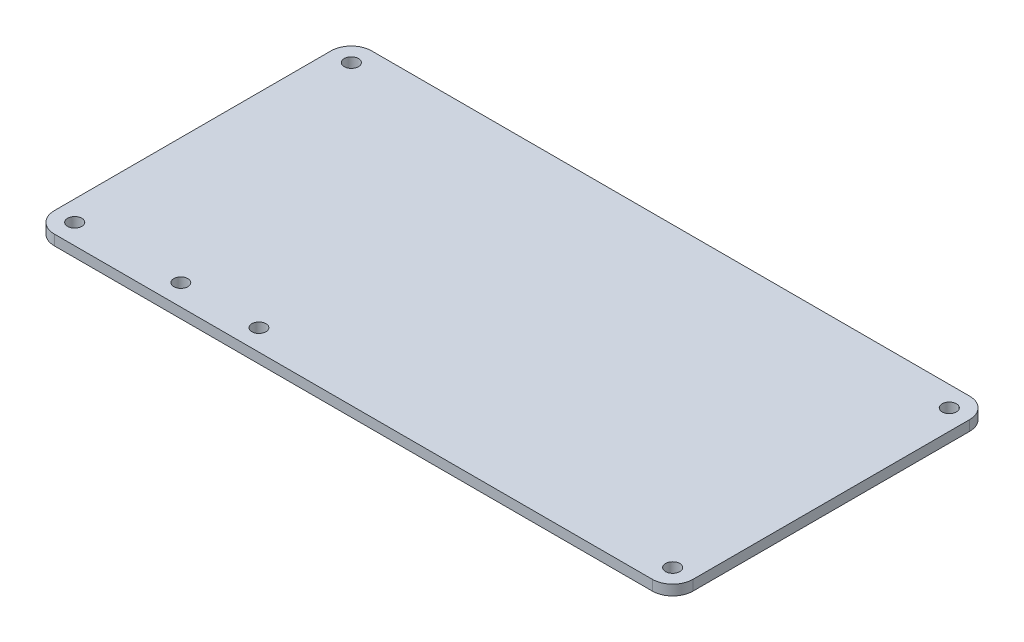
SolidWorks part; units mm, degrees
ref_plane "Front Plane" through (0, 0, 0) normal (0, 0, 1) x (1, 0, 0)
ref_plane "Top Plane" through (0, 0, 0) normal (0, 1, 0) x (1, 0, 0)
ref_plane "Right Plane" through (0, 0, 0) normal (1, 0, 0) x (0, 0, -1)
sketch "Sketch1" plane through (0, 0, 0) normal (0, 1, 0) x (1, 0, 0)
  line L0 (49.8475, 0) -> (49.8475, 49.53) construction
  line L1 (3.175, 0) -> (96.52, 0)
  line L2 (0, 3.175) -> (0, 46.355)
  line L3 (3.175, 49.53) -> (96.52, 49.53)
  line L4 (99.695, 3.175) -> (99.695, 46.355)
  line L5 (49.8475, 24.765) -> (0, 24.765) construction
  circle A0 centre (3.175, 46.355) radius 1.1112
  circle A1 centre (3.175, 46.355) radius 2.2225 construction
  arc A2 (3.175, 49.53) -> (0, 46.355) centre (3.175, 46.355) ccw
  circle A3 centre (96.52, 46.355) radius 1.1113
  circle A4 centre (96.52, 46.355) radius 2.2225 construction
  arc A5 (96.52, 49.53) -> (99.695, 46.355) centre (96.52, 46.355) cw
  circle A6 centre (96.52, 3.175) radius 1.1113
  circle A7 centre (96.52, 3.175) radius 2.2225 construction
  arc A8 (96.52, 0) -> (99.695, 3.175) centre (96.52, 3.175) ccw
  arc A9 (3.175, 0) -> (0, 3.175) centre (3.175, 3.175) cw
  circle A10 centre (3.175, 3.175) radius 2.2225 construction
  circle A11 centre (3.175, 3.175) radius 1.1112
  dimension "D4" = 3.175
  dimension "D5" = 4.445
  dimension "D1" = 2.2225
  dimension "D3" = 3.175
extrude "Boss-Extrude1" add sketch "Sketch1" along normal blind 1.6
sketch "Sketch2" plane through (0, 1.6, 0) normal (0, 1, 0) x (1, 0, 0)
  line L0 (3.175, 0) -> (96.52, 0) construction
  line L1 (0, 46.355) -> (0, 3.175) construction
  circle A0 centre (19.6125, 3.302) radius 1.1
  circle A1 centre (31.8025, 3.302) radius 1.1
  dimension "D1" = 2.2
  dimension "D2" = 2.2
  dimension "D4" = 3.302
  dimension "D3" = 12.19
  dimension "D5" = 19.6125
extrude "Cut-Extrude1" cut sketch "Sketch2" against normal through all
